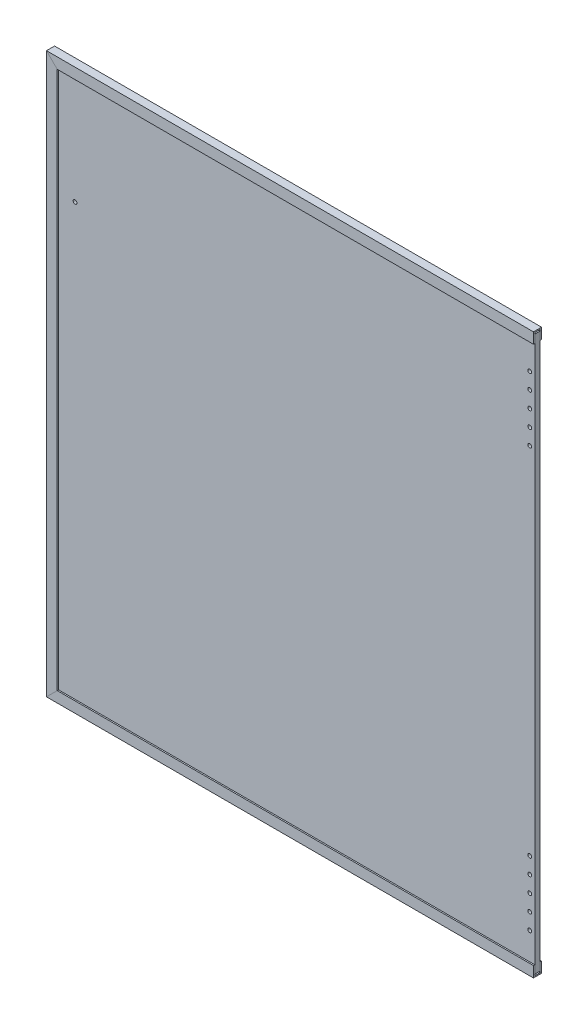
SolidWorks part; units mm, degrees
material "PC High Viscosity"
ref_plane "Front Plane" through (0, 0, 0) normal (0, 0, 1) x (1, 0, 0)
ref_plane "Top Plane" through (0, 0, 0) normal (0, 1, 0) x (1, 0, 0)
ref_plane "Right Plane" through (0, 0, 0) normal (1, 0, 0) x (0, 0, -1)
sketch "Shelf opening" plane through (0, 0, 0) normal (0, 0, 1) x (1, 0, 0)
  line L1 (0, 0) -> (577.85, 0)
  line L2 (0, 0) -> (0, 635)
  line L3 (0, 635) -> (577.85, 635)
  line L4 (577.85, 0) -> (577.85, 635)
  dimension "D1" = 577.85
  dimension "D2" = 635
sketch "Sketch2" plane through (0, 0, 0) normal (0, 0, 1) x (1, 0, 0)
  line L0 (577.85, 0) -> (577.85, 635) construction
  line L1 (3.175, 647.7) -> (577.85, 647.7)
  line L2 (3.175, 647.7) -> (3.175, -12.7)
  line L3 (3.175, -12.7) -> (577.85, -12.7)
  line L4 (577.85, 647.7) -> (577.85, -12.7)
  line L5 (0, 635) -> (577.85, 635) construction
  line L6 (0, 0) -> (0, 635) construction
  line L7 (0, 0) -> (577.85, 0) construction
  dimension "D1" = 12.7
  dimension "D2" = 3.175
  dimension "D3" = 12.7
extrude "Frame outer dimensions" add sketch "Sketch2" along normal mid plane 9.525
sketch "Sketch3" plane through (0, 0, 4.7625) normal (0, 0, 1) x (1, 0, 0)
  line L0 (577.85, -12.7) -> (577.85, 647.7) construction
  line L1 (577.85, 635) -> (15.875, 635)
  line L2 (577.85, 635) -> (577.85, 0)
  line L3 (577.85, 0) -> (15.875, 0)
  line L4 (15.875, 635) -> (15.875, 0)
  line L5 (577.85, 647.7) -> (3.175, 647.7) construction
  line L6 (3.175, 647.7) -> (3.175, -12.7) construction
  line L7 (3.175, -12.7) -> (577.85, -12.7) construction
  dimension "D1" = 12.7
  dimension "D2" = 12.7
  dimension "D3" = 12.7
extrude "Frame inner dimensions" cut sketch "Sketch3" against normal through all
sketch "Sketch4" plane through (0, 0, 0) normal (0, 0, 1) x (1, 0, 0)
  line L0 (577.85, 635) -> (577.85, 647.7) construction
  line L1 (577.85, 646.1125) -> (4.7625, 646.1125)
  line L2 (577.85, 646.1125) -> (577.85, -11.1125)
  line L3 (577.85, -11.1125) -> (4.7625, -11.1125)
  line L4 (4.7625, 646.1125) -> (4.7625, -11.1125)
  line L5 (577.85, 647.7) -> (3.175, 647.7) construction
  line L6 (3.175, 647.7) -> (3.175, -12.7) construction
  line L7 (3.175, -12.7) -> (577.85, -12.7) construction
  dimension "D1" = 1.5875
  dimension "D2" = 1.5875
  dimension "D3" = 1.5875
extrude "Frame profile" cut sketch "Sketch4" along normal offset from surface 1.5875 and the other way offset from surface 1.5875 up to face at (293.6875, 317.5, 4.7625) other way up to face at (293.6875, 317.5, -4.7625)
sketch "Frame sections" plane through (0, 0, 4.7625) normal (0, 0, 1) x (1, 0, 0)
  line L0 (3.175, 647.7) -> (15.875, 635)
  line L1 (3.175, -12.7) -> (15.875, 0)
split "Frame section split" trim tools "Frame sections" bodies to split 103 resulting bodies 105 106 107
sketch "Sketch5" plane through (0, 0, 0) normal (0, 0, 1) x (1, 0, 0)
  line L0 (577.85, 635) -> (577.85, 647.7) construction
  line L1 (577.85, 644.525) -> (6.35, 644.525)
  line L2 (577.85, 644.525) -> (577.85, -9.525)
  line L3 (577.85, -9.525) -> (6.35, -9.525)
  line L4 (6.35, 644.525) -> (6.35, -9.525)
  line L5 (4.7625, 646.1125) -> (577.85, 646.1125) construction
  line L6 (4.7625, -11.1125) -> (4.7625, 646.1125) construction
  line L7 (577.85, -11.1125) -> (4.7625, -11.1125) construction
  dimension "D1" = 1.5875
  dimension "D2" = 1.5875
  dimension "D3" = 1.5875
  dimension "D4" = 571.5
  dimension "D5" = 654.05
extrude "Door panel" add sketch "Sketch5" along normal mid plane 5.588 separate body
sketch "Hinge positions" plane through (0, 0, 2.794) normal (0, 0, 1) x (1, 0, 0)
  line L0 (577.85, -9.525) -> (577.85, 644.525) construction
  line L1 (577.85, 612.775) -> (565.15, 612.775)
  line L2 (577.85, 612.775) -> (577.85, 517.525)
  line L3 (577.85, 517.525) -> (565.15, 517.525)
  line L4 (565.15, 612.775) -> (565.15, 517.525)
  line L5 (565.15, 117.475) -> (577.85, 117.475)
  line L6 (565.15, 117.475) -> (565.15, 22.225)
  line L7 (565.15, 22.225) -> (577.85, 22.225)
  line L8 (577.85, 117.475) -> (577.85, 22.225)
  line L10 (0, 0) -> (577.85, 0) construction
  line L11 (0, 635) -> (577.85, 635) construction
  dimension "D1" = 95.25
  dimension "D2" = 12.7
  dimension "D3" = 22.225
  dimension "D4" = 22.225
  dimension "D5" = 495.3
sketch "Sketch8" plane through (0, 0, 2.794) normal (0, 0, 1) x (1, 0, 0)
  line L0 (565.15, 69.85) -> (577.85, 69.85) construction
  line L2 (565.15, 117.475) -> (565.15, 22.225) construction
  line L3 (577.85, 117.475) -> (577.85, 22.225) construction
  line L4 (565.15, 565.15) -> (577.85, 565.15) construction
  line L6 (565.15, 612.775) -> (565.15, 517.525) construction
  line L7 (577.85, 612.775) -> (577.85, 517.525) construction
  point P0 (571.5, 31.75)
  point P11 (571.5, 50.8)
  point P12 (571.5, 69.85)
  point P13 (571.5, 88.9)
  point P14 (571.5, 107.95)
  point P15 (571.5, 546.1)
  point P16 (571.5, 565.15)
  point P17 (571.5, 584.2)
  point P18 (571.5, 603.25)
  point P19 (571.5, 527.05)
  dimension "D3" = 19.05
  dimension "D1" = 5
  dimension "D2" = 2
hole_wizard "#8 Clearance Hole1" positions "Sketch8" profile "Sketch9" hole size "#8" standard "ANSI Inch" end condition through all
sketch "Sketch9" plane through (571.5, 31.75, 2.794) normal (1, 0, 0) x (0, -1, 0)
  line L0 (0, 0) -> (0, 7.5565)
  line L1 (0, 7.5565) -> (2.2479, 7.5565)
  line L2 (2.2479, 7.5565) -> (2.2479, 0)
  line L5 (2.2479, 0) -> (0, 0)
  line L11 (0, -6.35) -> (0, 107.95) construction
  dimension "Thru Hole Dia." = 4.4958
  dimension "Thru Hole Depth" = 7.5565
sketch "Handle positions" plane through (0, 0, 2.794) normal (0, 0, 1) x (1, 0, 0)
  line L1 (6.35, 644.525) -> (44.45, 644.525)
  line L2 (6.35, 644.525) -> (6.35, 495.3)
  line L3 (6.35, 495.3) -> (44.45, 495.3)
  line L4 (44.45, 644.525) -> (44.45, 495.3)
  line L5 (6.35, 644.525) -> (6.35, -9.525) construction
  line L6 (577.85, 644.525) -> (6.35, 644.525) construction
  dimension "D1" = 149.225
  dimension "D2" = 38.1
sketch "Sketch11" plane through (0, 0, 2.794) normal (0, 0, 1) x (1, 0, 0)
  line L0 (34.925, 508) -> (34.925, 635) construction
  line L2 (6.35, 644.525) -> (6.35, 495.3) construction
  line L3 (6.35, 644.525) -> (44.45, 644.525) construction
  point P0 (34.925, 635)
  point P2 (34.925, 508)
  dimension "D1" = 28.575
  dimension "D2" = 9.525
  dimension "D3" = 136.525
hole_wizard "#8 Clearance Hole2" positions "Sketch11" profile "Sketch12" hole size "#8" standard "ANSI Inch" end condition through all
sketch "Sketch12" plane through (34.925, 635, 2.794) normal (1, 0, 0) x (0, -1, 0)
  line L0 (0, 0) -> (0, 7.5565)
  line L1 (0, 7.5565) -> (2.2479, 7.5565)
  line L2 (2.2479, 7.5565) -> (2.2479, 0)
  line L5 (2.2479, 0) -> (0, 0)
  line L11 (0, -6.35) -> (0, 107.95) construction
  dimension "Thru Hole Dia." = 4.4958
  dimension "Thru Hole Depth" = 7.5565
mirror "Mirror1" about plane through (0, 0, 0) normal (1, 0, 0) of bodies 105 106 107 114 108
delete or keep bodies "Body-Delete/Keep 1" type keep bodies bodies 105 106 107 114
delete or keep bodies "Body-Delete/Keep 2" [suppressed] type keep bodies bodies 109 110 111 112
